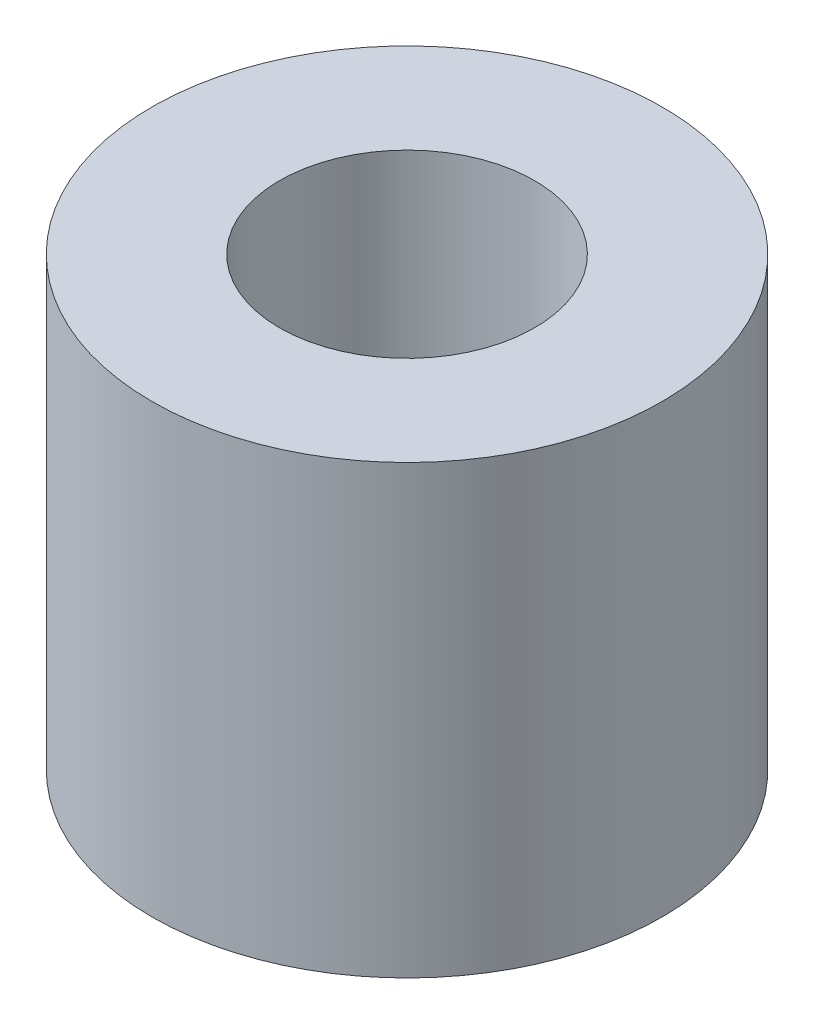
SolidWorks part; units mm, degrees
ref_plane "Front Plane" through (0, 0, 0) normal (0, 0, 1) x (1, 0, 0)
ref_plane "Top Plane" through (0, 0, 0) normal (0, 1, 0) x (1, 0, 0)
ref_plane "Right Plane" through (0, 0, 0) normal (1, 0, 0) x (0, 0, -1)
sketch "Sketch1" plane through (0, 0, 0) normal (0, 1, 0) x (1, 0, 0)
  circle A0 centre (0, 0) radius 6.35
  circle A1 centre (0, 0) radius 3.175
  dimension "D1" = 12.7
  dimension "D2" = 6.35
extrude "Boss-Extrude1" add sketch "Sketch1" along normal mid plane 11.1125
